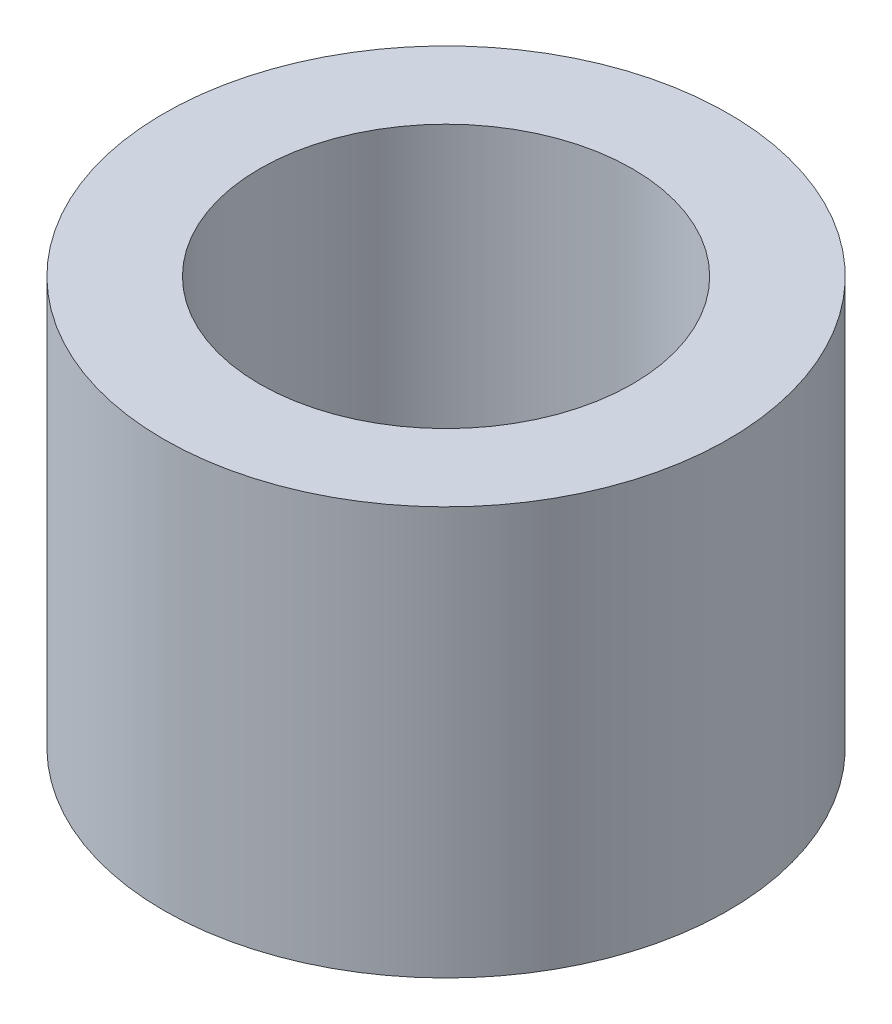
SolidWorks part; units mm, degrees
ref_plane "Front Plane" through (0, 0, 0) normal (0, 0, 1) x (1, 0, 0)
ref_plane "Top Plane" through (0, 0, 0) normal (0, 1, 0) x (1, 0, 0)
ref_plane "Right Plane" through (0, 0, 0) normal (1, 0, 0) x (0, 0, -1)
sketch "Sketch1" plane through (0, 0, 0) normal (0, 1, 0) x (1, 0, 0)
  circle A0 centre (0, 0) radius 20
  dimension "SLEEVE_OD" = 40
extrude "Boss-Extrude1" add sketch "Sketch1" along normal blind 28.9111
sketch "Sketch2" plane through (0, 0, 0) normal (0, 1, 0) x (1, 0, 0)
  circle A0 centre (0, 0) radius 13.2089
  dimension "BORE_D" = 26.4179
extrude "Cut-Extrude1" cut sketch "Sketch2" along normal through all
chamfer "Chamfer1" distance 3.2775 angle 66.098 rebuild error yes
